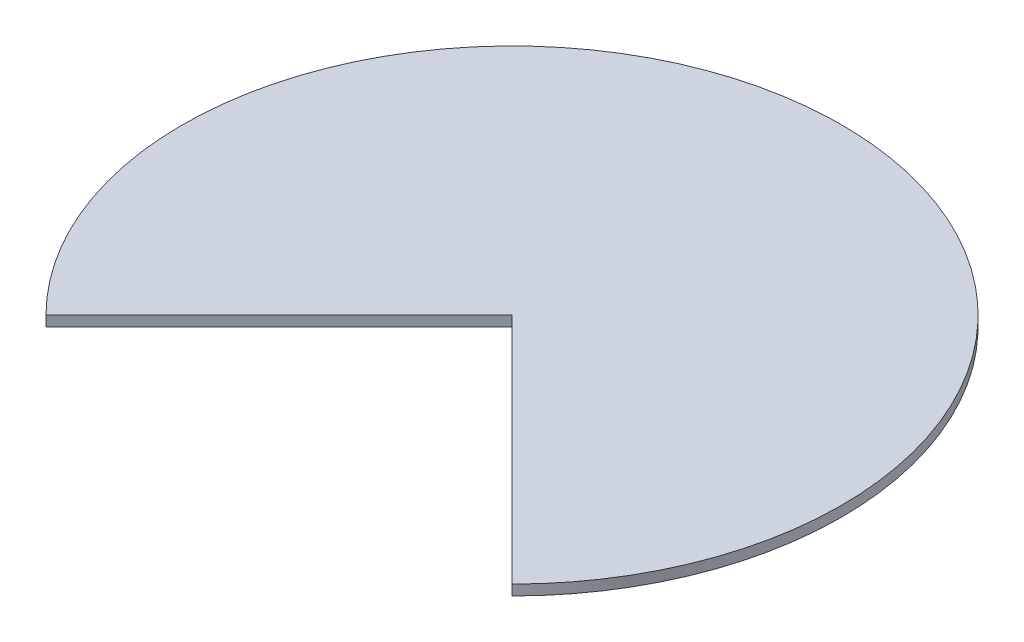
SolidWorks part; units mm, degrees
ref_plane "Front Plane" through (0, 0, 0) normal (0, 0, 1) x (1, 0, 0)
ref_plane "Top Plane" through (0, 0, 0) normal (0, 1, 0) x (1, 0, 0)
ref_plane "Right Plane" through (0, 0, 0) normal (1, 0, 0) x (0, 0, -1)
sketch "Sketch1" plane through (0, 0, 0) normal (0, 1, 0) x (1, 0, 0)
  line L0 (0, 0) -> (-143.6841, -143.6841)
  line L1 (0, 0) -> (143.6841, -143.6841)
  line L2 (0, 0) -> (0, -74434.7764) construction
  arc A0 (143.6841, -143.6841) -> (-143.6841, -143.6841) centre (0, 0) ccw
  dimension "D1" = 203.2
extrude "Boss-Extrude1" add sketch "Sketch1" along normal mid plane 6.35
